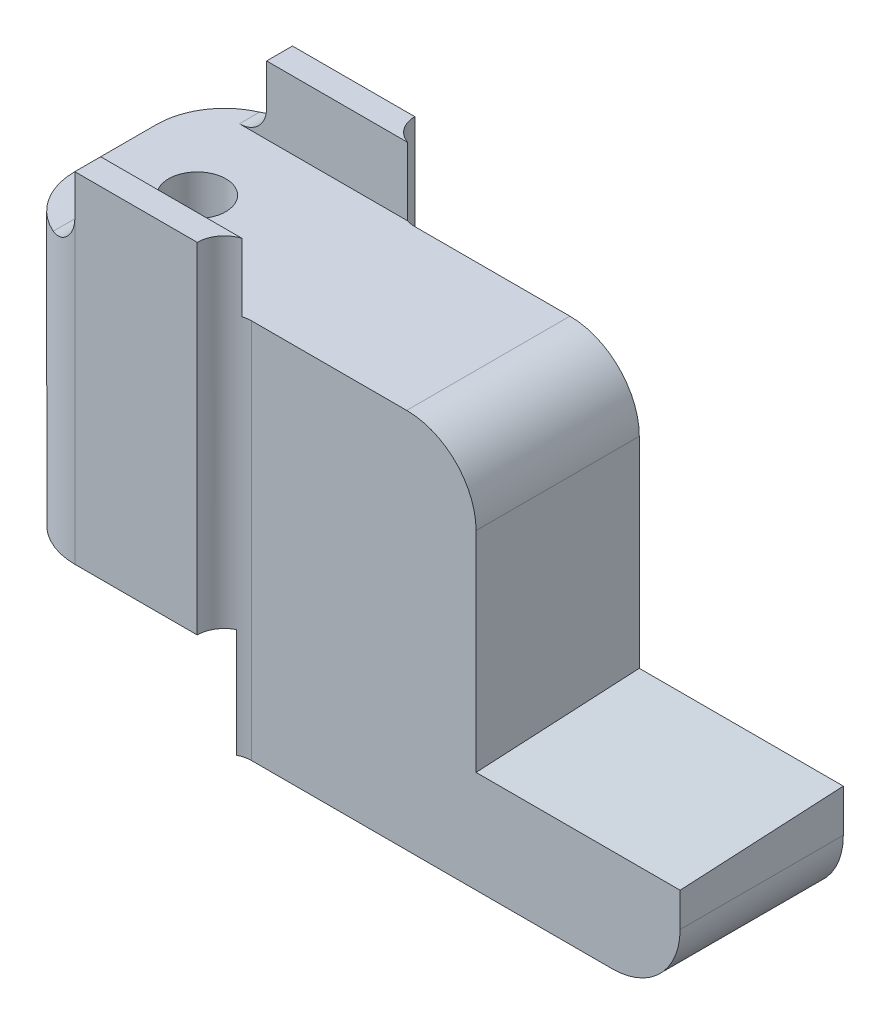
SolidWorks part; units mm, degrees
ref_plane "Front Plane" through (0, 0, 0) normal (0, 0, 1) x (1, 0, 0)
ref_plane "Top Plane" through (0, 0, 0) normal (0, 1, 0) x (1, 0, 0)
ref_plane "Right Plane" through (0, 0, 0) normal (1, 0, 0) x (0, 0, -1)
sketch "Sketch1" plane through (0, 0, 0) normal (0, 1, 0) x (1, 0, 0)
  line L5 (-6, 8) -> (6, 8)
  line L6 (-6, 8) -> (-6, -8)
  line L7 (-6, -8) -> (6, -8)
  line L8 (6, 8) -> (6, -8)
  line L9 (-6, 8) -> (6, -8) construction
  line L10 (-6, -8) -> (6, 8) construction
  line L11 (6, 8) -> (8, 8)
  line L12 (6, 8) -> (6, -8)
  line L13 (6, -8) -> (8, -8)
  line L14 (8, 8) -> (8, -8)
  circle A0 centre (0, 0) radius 2.1
  point P0 (0, 0)
  dimension "D1" = 4.2
  dimension "D2" = 16
  dimension "D3" = 6
  dimension "D4" = 2
extrude "Boss-Extrude1" add sketch "Sketch1" along normal blind 20 contours L8 L5 L6 L7 A0 | L14 L11 L8 L13 region at (0, 0, -7.8) region at (7, 0, 0)
fillet "Fillet1" radius 5 2 edges at (-6, 10, -8) (-6, 10, 8)
sketch "Sketch2" plane through (0, 20, 0) normal (0, 1, 0) x (1, 0, 0)
  line L0 (8, 0) -> (-6, 0) construction
  line L1 (8, 8) -> (-1, 8)
  line L2 (8, 8) -> (8, 6.1)
  line L3 (8, 6.1) -> (-1, 6.1)
  line L4 (-1, 8) -> (-1, 6.1)
  line L5 (8, 8) -> (8, -8) construction
  line L6 (-6, 3) -> (-6, -3) construction
  line L7 (-1, -8) -> (-1, -6.1)
  line L8 (8, -6.1) -> (-1, -6.1)
  line L9 (8, -8) -> (8, -6.1)
  line L10 (8, -8) -> (-1, -8)
  dimension "D1" = 1.9
extrude "Boss-Extrude2" add sketch "Sketch2" along normal blind 5
sketch "Sketch4" plane through (8, 0, 0) normal (1, 0, 0) x (0, 0, -1)
  line L0 (8, 25) -> (8, 0) construction
  line L1 (-6, 0) -> (6, 0)
  line L2 (-6, 0) -> (-6, 20)
  line L3 (-6, 20) -> (6, 20)
  line L4 (6, 0) -> (6, 20)
  line L6 (6.1, 20) -> (-6.1, 20) construction
  point P6 (0, 0)
  dimension "D1" = 2
extrude "Boss-Extrude3" add sketch "Sketch4" along normal offset from surface (18.5 mm away) 32.5 up to face at (-6, 10, 0)
fillet "Fillet2" radius 5.1 1 edges at (26.5, 20, 0)
sketch "Sketch5" plane through (0, 0, 0) normal (0, -1, 0) x (1, 0, 0)
  line L0 (26.5, 6) -> (8, 6) construction
  line L1 (9.1, 6) -> (26.5, 6)
  line L2 (9.1, 6) -> (9.1, -6)
  line L3 (9.1, -6) -> (26.5, -6)
  line L4 (26.5, 6) -> (26.5, -6)
  line L5 (9.1, 6) -> (26.5, -6) construction
  line L6 (9.1, -6) -> (26.5, 6) construction
  line L7 (26.5, 6) -> (26.5, -6) construction
  circle A0 centre (0, 0) radius 2.1 construction
  point P0 (17.8, 0)
  dimension "D1" = 9.1
extrude "Boss-Extrude4" add sketch "Sketch5" along normal blind 8
sketch "Sketch8" plane through (26.5, 0, 0) normal (1, 0, 0) x (0, 0, -1)
  line L0 (-6, -8) -> (-6, -0.5)
  line L1 (-6, 14.9) -> (-6, -8) construction
  line L2 (-6, -0.5) -> (6, 0.1289)
  line L3 (6, 0) -> (6, 20) construction
  line L4 (6, 0.1289) -> (6, -8)
  line L5 (6, -8) -> (-6, -8)
  line L6 (-6, -0.5) -> (6, -0.5) construction
  dimension "D1" = 7.5
  dimension "D2" = 3
extrude "Boss-Extrude5" add sketch "Sketch8" along normal blind 15
fillet "Fillet4" radius 5 1 edges at (41.5, -8, 0)
fillet "Fillet5" radius 2 4 edges at (-1, 20, -7.05) (-1, 20, 7.05) (8, 10, -6) (8, 10, 6)
